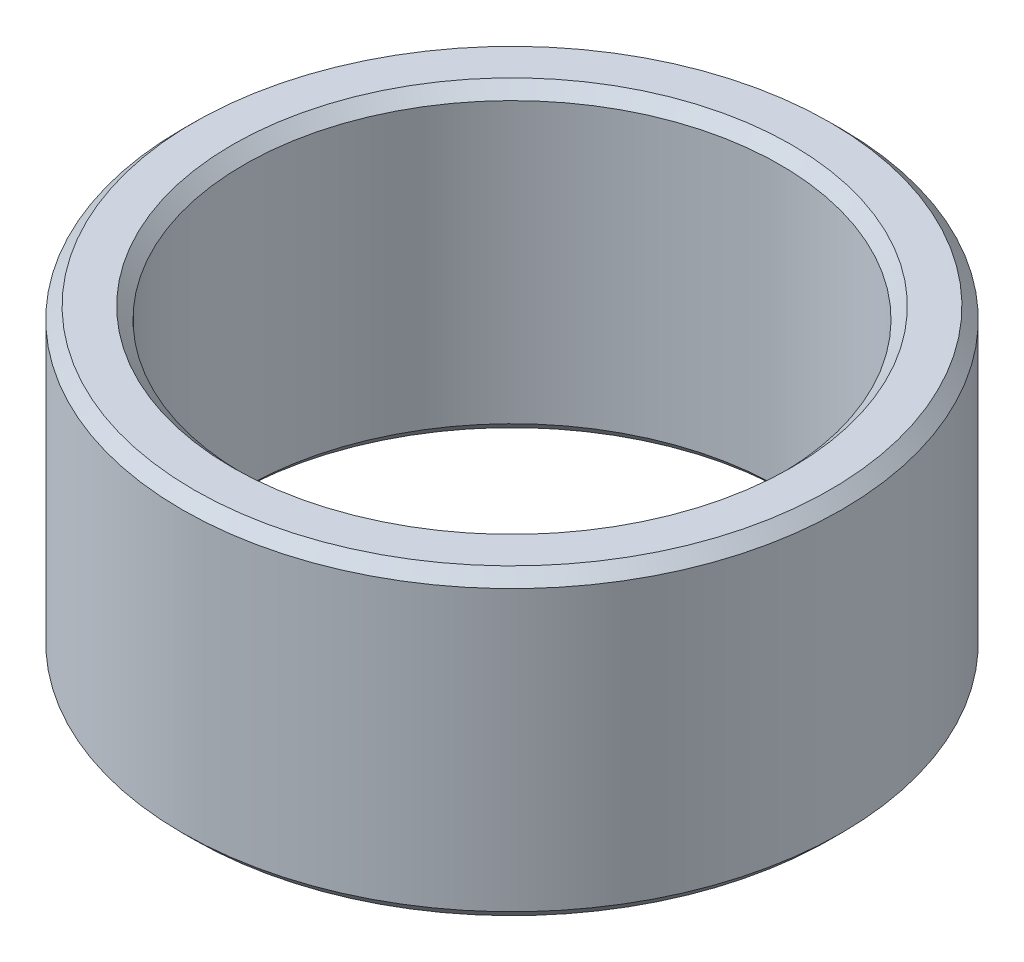
SolidWorks part; units mm, degrees
ref_plane "Front Plane" through (0, 0, 0) normal (0, 0, 1) x (1, 0, 0)
ref_plane "Top Plane" through (0, 0, 0) normal (0, 1, 0) x (1, 0, 0)
ref_plane "Right Plane" through (0, 0, 0) normal (1, 0, 0) x (0, 0, -1)
sketch "Sketch1" plane through (0, 0, 0) normal (0, 1, 0) x (1, 0, 0)
  circle A0 centre (0, 0) radius 32.5
  dimension "SLEEVE_OD" = 65
extrude "Boss-Extrude1" add sketch "Sketch1" along normal blind 29.8582
sketch "Sketch2" plane through (0, 0, 0) normal (0, 1, 0) x (1, 0, 0)
  circle A0 centre (0, 0) radius 26.4214
  dimension "BORE_D" = 52.8428
extrude "Cut-Extrude1" cut sketch "Sketch2" along normal through all
chamfer "Chamfer1" distance 1.137 angle 45 4 edges at (0, 29.8582, 26.4214) (0, 0, 26.4214) (0, 0, 32.5) (0, 29.8582, 32.5)
